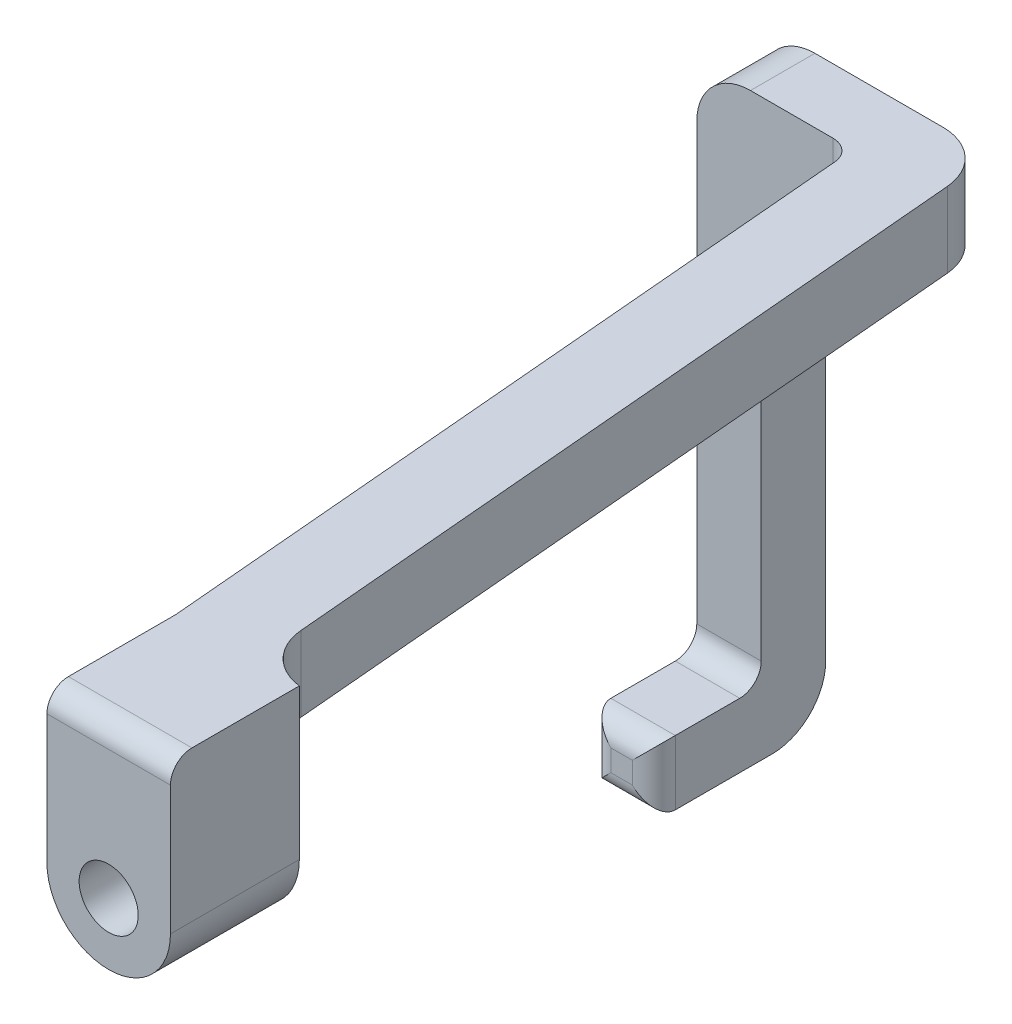
SolidWorks part; units mm, degrees
ref_plane "Front Plane" through (0, 0, 0) normal (1, 0, 0) x (0, 1, 0)
ref_plane "Top Plane" through (0, 0, 0) normal (0, 0, 1) x (0, 1, 0)
ref_plane "Right Plane" through (0, 0, 0) normal (0, 1, 0) x (-1, 0, 0)
sketch "Sketch1" plane through (0, 0, 0) normal (0, 0, 1) x (0, 1, 0)
  line L0 (0, 0) -> (1.375, 0) construction
  line L3 (0, 2.875) -> (7, 2.875)
  line L4 (0, -2.875) -> (7, -2.875)
  line L5 (7, -2.875) -> (7, 2.875)
  arc A0 (0, 2.875) -> (0, -2.875) centre (0, 0) ccw
  circle A3 centre (0, 0) radius 1.375
  point P2 (0, 0)
  dimension "D1" = 2.75
  dimension "D2" = 2.875
  dimension "D3" = 7
extrude "Boss-Extrude1" add sketch "Sketch1" along normal blind 6
sketch "Sketch2" plane through (0, 0, 0) normal (0, 0, -1) x (1, 0, 0)
  line L0 (2.875, -7) -> (-2.875, -7) construction
  line L1 (0.875, -7) -> (-2.875, -7)
  line L2 (2.875, 0) -> (2.875, -7) construction
  line L3 (-2.875, -7) -> (-2.875, 0) construction
  line L4 (0.875, -3.5) -> (0.875, -7)
  line L5 (-2.875, -7) -> (-2.875, -3.5)
  line L6 (-2.875, -3.5) -> (0.875, -3.5)
  dimension "D1" = 2
ref_plane "Plane1" through (0, 0, -37.5) normal (0, 0, -1) x (-1, 0, 0)
sketch "Sketch8" plane through (0, 0, -37.5) normal (0, 0, -1) x (-1, 0, 0)
  line L0 (-0.875, 3.5) -> (-0.875, 7) construction
  line L1 (2.875, 3.5) -> (-0.875, 3.5) construction
  line L2 (2.875, 7) -> (2.875, 3.5) construction
  line L3 (-0.875, 7) -> (2.875, 7) construction
  line L4 (-0.875, 3.5) -> (-0.875, 7) construction
  line L5 (2.875, 3.5) -> (-0.875, 3.5) construction
  line L6 (2.875, 7) -> (2.875, 3.5) construction
  line L7 (-0.875, 7) -> (2.875, 7) construction
  line L8 (2.375, 3.5) -> (2.375, 7)
  line L9 (6.125, 3.5) -> (6.125, 7)
  line L10 (2.375, 7) -> (6.125, 7)
  line L11 (6.125, 3.5) -> (2.375, 3.5)
  dimension "D1" = 3.25
loft "Loft1" add profiles "Sketch2", "Sketch8"
sketch "Sketch9" plane through (0, 0, 0) normal (1, 0, 0) x (0, 1, 0)
  line L0 (3.5, 0) -> (3.5, -37.5) construction
  line L1 (7, 0) -> (7, -37.5) construction
  line L2 (3.5, -34.5) -> (3.5, -37.5)
  line L3 (7, -34.5) -> (7, -37.5)
  line L4 (7, -37.5) -> (3.5, -37.5)
  line L6 (7, -34.5) -> (3.5, -34.5)
  dimension "D1" = 3
extrude "Boss-Extrude2" add sketch "Sketch9" against normal blind 7 and the other way up to surface from vertex
sketch "Sketch10" plane through (0, 7, 0) normal (0, 1, 0) x (-1, 0, 0)
  line L0 (13.125, -37.5) -> (6.125, -37.5) construction
  line L1 (13.125, -37.5) -> (13.125, -34.5) construction
  line L2 (5.865, -34.5) -> (13.125, -34.5) construction
  line L3 (13.125, -37.5) -> (10.125, -37.5)
  line L4 (13.125, -37.5) -> (13.125, -34.5)
  line L5 (10.125, -34.5) -> (13.125, -34.5)
  line L6 (10.125, -34.5) -> (10.125, -37.5)
  dimension "D1" = 3
extrude "Boss-Extrude3" add sketch "Sketch10" against normal blind 23.25 from surface
sketch "Sketch11" plane through (0, 0, -34.5) normal (0, 0, 1) x (1, 0, 0)
  line L0 (-13.125, -19.75) -> (-13.125, 7) construction
  line L2 (-10.125, -19.75) -> (-10.125, 3.5) construction
  line L3 (-13.125, -16.75) -> (-13.125, -19.75)
  line L4 (-13.125, -16.75) -> (-10.125, -16.75)
  line L5 (-10.125, -16.75) -> (-10.125, -19.75)
  line L6 (-10.125, -19.75) -> (-13.125, -19.75)
  line L7 (-13.125, -19.75) -> (-10.125, -19.75) construction
  dimension "D1" = 3
extrude "Boss-Extrude4" add sketch "Sketch11" along normal blind 5
fillet "Fillet1" radius 2.5 11 edges at (-13.125, 7, -36) (-11.625, -19.75, -37.5) (-10.125, 3.5, -36)
fillet "Fillet2" radius 1 7 edges at (-10.125, -18.25, -29.5) (-11.625, -19.75, -29.5) (-13.125, -18.25, -29.5) (-11.625, -16.75, -29.5) (0, 7, 6) (-5.865, 5.25, -34.5) (-11.625, -16.75, -34.5)
